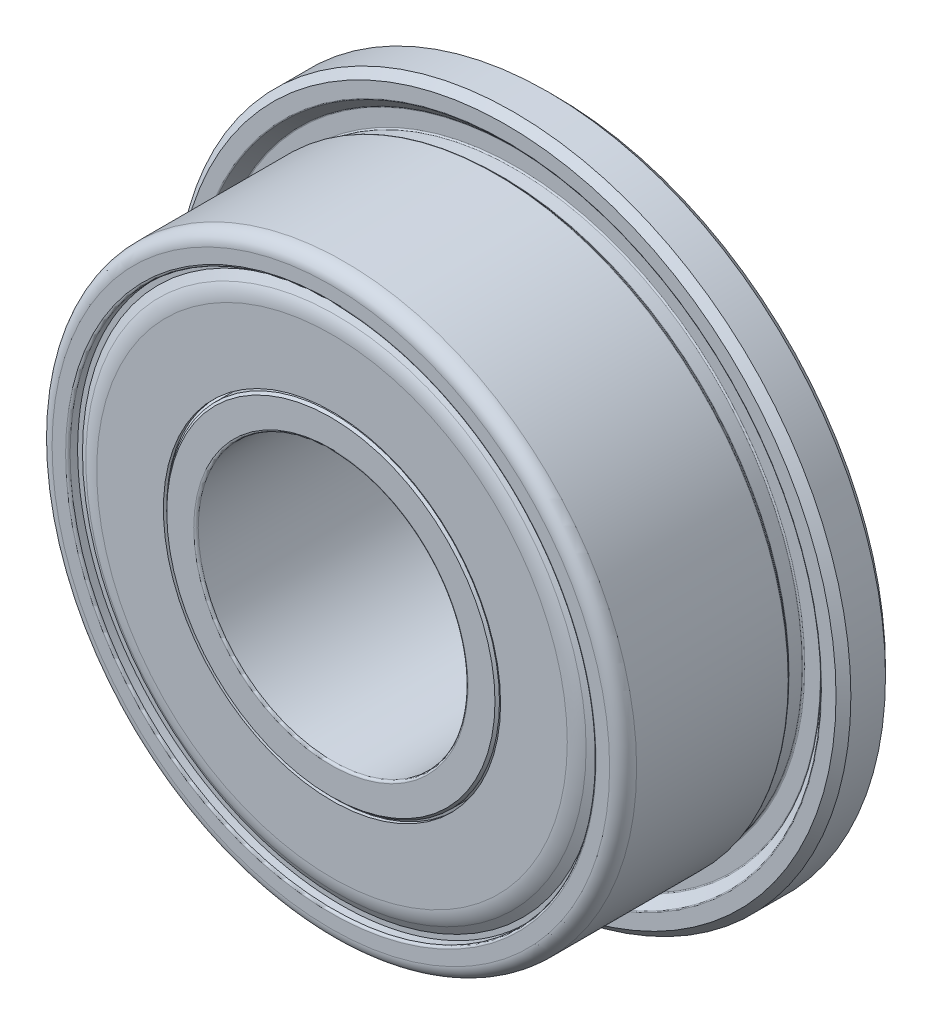
SolidWorks part; units mm, degrees
note: '?' marks a value the reader was unsure of.
ref_plane "Front Plane" through (0, 0, 0) normal (0, 0, 1) x (1, 0, 0)
ref_plane "Top Plane" through (0, 0, 0) normal (0, 1, 0) x (1, 0, 0)
ref_plane "Right Plane" through (0, 0, 0) normal (1, 0, 0) x (0, 0, -1)
sketch "Sketch1" plane through (0, 0, 0) normal (1, 0, 0) x (0, 0, -1)
  line L0 (-2.5, 0) -> (2.5, 0) construction
  line L1 (0, 6.5) -> (0, -6.5) construction
  line L2 (2.5, 6.5) -> (-2.5, 6.5)
  line L4 (-2.5, 6.5) -> (-2.5, 5.85)
  line L5 (-2.5, 5.85) -> (-0.7899, 5.85)
  line L6 (2.5, 5.85) -> (0.7899, 5.85)
  line L7 (2.5, 6.5) -> (2.5, 5.85)
  line L9 (0, 6.5) -> (0, 4.75) construction
  line L10 (0, 4.75) -> (0, 3) construction
  line L11 (-2.5, -5.85) -> (-2.5, 5.85) construction
  line L12 (1.4, -7.5) -> (2.5, -7.5)
  line L13 (1.4, -7.5) -> (1.4, 7.5)
  line L14 (1.4, 7.5) -> (2.5, 7.5)
  line L15 (2.5, -7.5) -> (2.5, 7.5)
  line L16 (1.4, -7.5) -> (2.5, 7.5) construction
  line L17 (1.4, 7.5) -> (2.5, -7.5) construction
  line L18 (-2.5, -3.7) -> (-2.5, 3.7)
  line L24 (0, -6.5) -> (-2.5, -6.5)
  line L25 (0, 3) -> (0, 6.5) construction
  line L26 (-2.5, 3.7) -> (-2.5, 3)
  line L27 (-2.5, 3) -> (2.5, 3)
  line L28 (2.5, 3) -> (2.5, 3.7)
  line L29 (2.5, 3.7) -> (0.5899, 3.7)
  line L30 (-2.5, 3.7) -> (-0.5899, 3.7)
  line L31 (-0.7899, 5.85) -> (-0.7899, 5.42)
  line L32 (-0.7899, 5.42) -> (-0.5899, 5.42)
  line L33 (0.7899, 5.85) -> (0.7899, 5.42)
  line L34 (0.7899, 5.42) -> (0.5899, 5.42)
  arc A3 (-0.5899, 3.7) -> (0.5899, 3.7) centre (0, 4.75) ccw
  circle A5 centre (0, 4.5756) radius 1
  arc A6 (-0.5899, 5.42) -> (0.5899, 5.42) centre (0, 4.5756) cw
  point P7 (-2.5, 5.85)
  point P13 (-2.4, 5.85)
  point P14 (0, 3)
  point P15 (1.95, 0)
  point P22 (2.5, 0)
  point P25 (-2.5, 0)
  point P27 (-2.5, 0)
  point P28 (-2.3, 5.85)
  point P29 (-2.2, 5.85)
  point P30 (-2.1, 5.85)
  point P31 (-2, 5.85)
  point P32 (-1.9, 5.85)
  point P33 (-1.8, 5.85)
  point P46 (0, 5.6056)
  point P50 (0, 3.5456)
  point P51 (0, 3.5756)
  point P52 (0, 5.5756)
  dimension "D3" = 2
  dimension "Shaft Dia" = 6
  dimension "Flange Thickness" = 1.1
  dimension "Flange OD" = 15
  dimension "D11" = 11.7
  dimension "D10" = 7.4
  dimension "Width" = 5
  dimension "OD" = 13
  dimension "D4" = 0.03
  dimension "D2" = 0.03
  dimension "D5" = 0.2
  dimension "D6" = 0.1
  dimension "D7" = 1.72
  dimension "D1" = 8
sketch "Sketch2" plane through (0, 0, 0) normal (0, 0, 1) x (1, 0, 0)
  line L0 (0, -3.7) -> (0, 3.7) construction
  circle A0 centre (0, 0) radius 3
  dimension "D1" = 6
sketch "Sketch3" plane through (0, 0, 0) normal (1, 0, 0) x (0, 0, -1)
  line L2 (-2.5, 6.5) -> (-2.5, 5.85) construction
  line L3 (2.5, 6.5) -> (-2.5, 6.5) construction
  line L4 (2.5, 6.5) -> (2.5, 5.85) construction
  line L5 (2.5, 5.85) -> (0.7899, 5.85) construction
  line L6 (-2.5, 5.85) -> (-0.7899, 5.85) construction
  line L13 (-2.5, 6.5) -> (-2.5, 5.85)
  line L21 (2.5, 6.5) -> (-2.5, 6.5)
  line L22 (2.5, 6.5) -> (2.5, 5.85)
  line L23 (2.5, 5.85) -> (0.7899, 5.85)
  line L24 (-2.5, 5.85) -> (-0.7899, 5.85)
  line L25 (2.5, 3) -> (-2.5, 3)
  line L27 (-2.5, 3) -> (-2.5, 3.7)
  line L28 (-2.5, 3.7) -> (-0.5899, 3.7)
  line L29 (0.7899, 5.85) -> (0.7899, 5.42) construction
  line L30 (2.5, 3) -> (2.5, 3.7)
  line L31 (2.5, -7.5) -> (2.5, 7.5) construction
  line L32 (2.5, 3.7) -> (0.5899, 3.7)
  line L33 (0.7899, 5.42) -> (0.5899, 5.42) construction
  line L34 (-0.7899, 5.42) -> (-0.5899, 5.42) construction
  line L35 (-0.7899, 5.85) -> (-0.7899, 5.42) construction
  line L36 (0.7899, 5.85) -> (0.7899, 5.42)
  line L37 (0.7899, 5.42) -> (0.5899, 5.42)
  line L38 (-0.7899, 5.42) -> (-0.5899, 5.42)
  line L39 (-0.7899, 5.85) -> (-0.7899, 5.42)
  arc A4 (0.5899, 5.42) -> (-0.5899, 5.42) centre (0, 4.5756) ccw construction
  arc A5 (-0.5899, 3.7) -> (0.5899, 3.7) centre (0, 4.75) ccw construction
  arc A6 (-0.5899, 3.7) -> (0.5899, 3.7) centre (0, 4.75) ccw
  arc A7 (0.5899, 5.42) -> (-0.5899, 5.42) centre (0, 4.5756) ccw
  point P15 (0, 3)
revolve "Revolve1" add sketch "Sketch3" angle 360 about L0
sketch "Sketch5" plane through (0, 0, 0) normal (1, 0, 0) x (0, 0, -1)
  line L0 (-1, 4.5756) -> (1, 4.5756)
  line L1 (0, 6.5) -> (0, -6.5) construction
  circle A0 centre (0, 4.5756) radius 1 construction
  arc A1 (-1, 4.5756) -> (1, 4.5756) centre (0, 4.5756) cw
revolve "Revolve3" add sketch "Sketch5" angle 360 about L0
ref_axis "Axis1" through (0, 0, -2.5) along (0, 0, 1)?
pattern_circular "CirPattern1" count 8 over 360 about axis through (0, 0, 0) along (0, 0, 1) of bodies 122
sketch "Sketch6" plane through (0, 0, 0) normal (1, 0, 0) x (0, 0, -1)
  line L1 (-2.475, 3.7) -> (-2.475, 5.2332)
  line L2 (-2.3866, 5.5632) -> (-2.2845, 5.74)
  line L4 (-2.2845, 5.74) -> (-2.1979, 5.74) construction
  line L5 (-2.2845, 5.74) -> (-2.2845, 5.85)
  line L6 (-2.2845, 5.85) -> (-2.1979, 5.85)
  line L7 (-2.1979, 5.74) -> (-2.4, 5.3899)
  line L8 (-2.4, 5.3899) -> (-2.4, 3.7)
  line L9 (-2.4, 3.7) -> (-2.475, 3.7)
  line L10 (0, 6.5) -> (0, -6.5) construction
  line L11 (-2.1979, 5.85) -> (-2.1979, 5.74)
  line L12 (-2.5, 5.85) -> (-0.7899, 5.85) construction
  line L14 (0, 6.5) -> (0, 5.6056) construction
  arc A0 (-2.475, 5.2332) -> (-2.3866, 5.5632) centre (-1.815, 5.2332) cw
  point P22 (-2.475, 5.41)
  dimension "D8" = 0.66
  dimension "D1" = 30
  dimension "D3" = 0.075
  dimension "D2" = 0.025
  dimension "D4" = 0.075
  dimension "D6" = 0.33
  dimension "D5" = 2.15
  dimension "D7" = 0.11
revolve "Revolve4" add sketch "Sketch6" angle 360 about L0
mirror "Mirror1" about plane through (0, 0, 0) normal (0, 0, 1) of bodies 138
sketch "Sketch9" plane through (0, 0, 2.475) normal (0, 0, 1) x (1, 0, 0)
  circle A2 centre (0, 0) radius 3.75
  circle A3 centre (0, 0) radius 3.75
  dimension "D1" = 0.05
extrude "Cut-Extrude1" cut sketch "Sketch9" against normal through all
sketch "Sketch7" plane through (0, 0, 0) normal (1, 0, 0) x (0, 0, -1)
  line L0 (2.5, 0) -> (-2.5, 0) construction
  line L2 (1.4, 7.5) -> (2.5, 7.5)
  line L3 (1.4, 7.5) -> (1.4, 5.85)
  line L4 (1.4, 5.85) -> (2.5, 5.85)
  line L5 (2.5, 7.5) -> (2.5, 5.85)
revolve "Revolve5" add sketch "Sketch7" angle 360 about L0
fillet "Fillet2" radius 0.3 1 edges at (6.5, 0, 2.5)
fillet "Fillet3" radius 0.05 4 edges at (5.85, 0, -2.5) (5.85, 0, 2.5) (5.85, 0, -0.7899) (5.85, 0, 0.7899)
fillet "Fillet6" radius 0.05 4 edges at (3.7, 0, -2.5) (3.7, 0, -0.5899) (3.7, 0, 0.5899) (3.7, 0, 2.5)
sketch "Sketch8" plane through (0, 0, 0) normal (1, 0, 0) x (0, 0, -1)
  line L7 (1.4, 7.5) -> (1.4, 6.5) construction
  line L8 (1.4, 7) -> (1.62, 6.78)
  line L9 (1.62, 6.78) -> (1.62, 6.39)
  line L10 (1.62, 6.39) -> (1.29, 6.39)
  line L11 (1.29, 6.39) -> (1.18, 6.5)
  line L12 (1.4, 6.5) -> (-2.2, 6.5) construction
  line L13 (1.18, 6.5) -> (1.4, 6.5)
  line L14 (1.4, 6.5) -> (1.4, 7)
  dimension "D1" = 45
  dimension "D2" = 45
  dimension "D3" = 0.22
  dimension "D4" = 0.11
  dimension "D5" = 0.11
revolve "Cut-Revolve1" cut sketch "Sketch8" angle 360 about L0
fillet "Fillet5" radius 0.03 5 edges at (6.5, 0, -1.18) (6.39, 0, -1.29) (6.39, 0, -1.62) (6.78, 0, -1.62) (7, 0, -1.4)
chamfer "Chamfer1" distance 0.165 angle 45 2 edges at (-7.5, 0, -1.4) (-7.5, 0, -2.5)
fillet "Fillet7" radius 0.05 2 edges at (3, 0, 2.5) (3, 0, -2.5)
equation "\"Balls@CirPattern1\"=\"D1@Sketch1\""
equation "\"D3@Sketch8\" = \"Flange Thickness@Sketch1\" * .2"
equation "\"D4@Sketch8\" = \"D3@Sketch8\" * .5"
equation "\"D5@Sketch8\" = \"D3@Sketch8\" * .5"
equation "\"D1@Chamfer1\"=\"Flange Thickness@Sketch1\"*.15"
equation "\"D1@Fillet6\"=\"D1@Fillet3\""
equation "\"D4@Sketch1\"=\"D2@Sketch1\""
equation "\"D7@Sketch1\" =  ( \"D11@Sketch1\" - \"D10@Sketch1\" )  * .40"
equation "\"D3@Sketch6\"=\"D4@Sketch6\""
equation "\"D8@Sketch6\"=\"D6@Sketch6\"*2"
